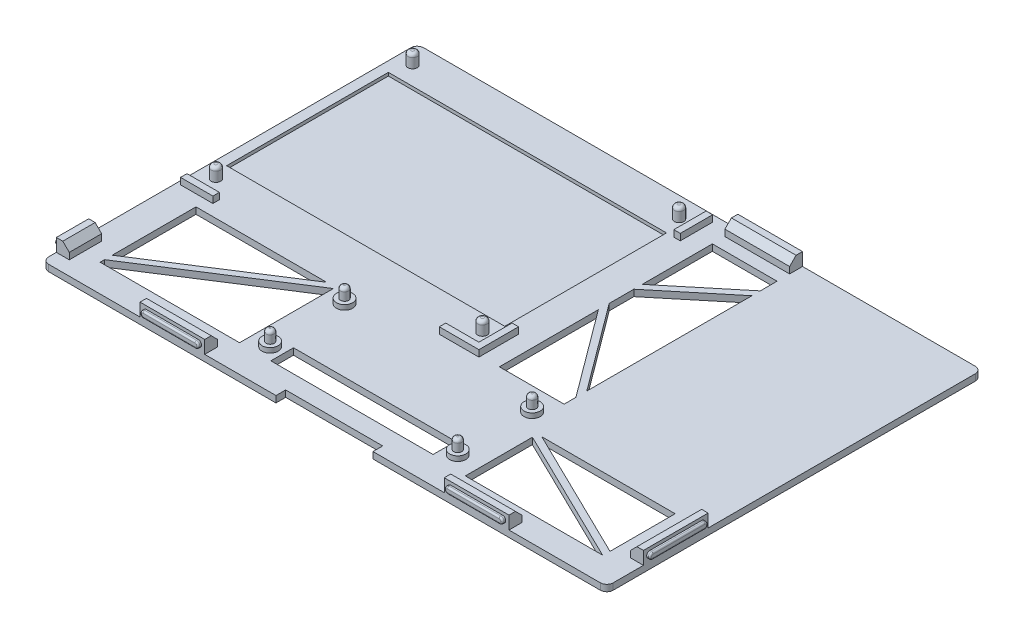
SolidWorks part; units mm, degrees
ref_plane "前基準面" through (0, 0, 0) normal (0, 0, 1) x (1, 0, 0)
ref_plane "上基準面" through (0, 0, 0) normal (0, 1, 0) x (1, 0, 0)
ref_plane "右基準面" through (0, 0, 0) normal (1, 0, 0) x (0, 0, -1)
sketch "草圖1" plane through (0, 0, 0) normal (0, 1, 0) x (1, 0, 0)
  line L0 (0, 57.975) -> (0, -57.975) construction
  line L1 (-87.275, 57.975) -> (87.275, 57.975)
  line L2 (-87.275, 57.975) -> (-87.275, -57.975)
  line L3 (-87.275, -57.975) -> (87.275, -57.975)
  line L4 (87.275, 57.975) -> (87.275, -57.975)
  line L5 (-87.275, 57.975) -> (87.275, -57.975) construction
  line L6 (-87.275, -57.975) -> (87.275, 57.975) construction
  line L7 (-87.275, 0) -> (87.275, 0) construction
  point P0 (0, 0)
  dimension "D1" = 174.55
  dimension "D2" = 115.95
extrude "填料-伸長1" add sketch "草圖1" along normal blind 2
sketch "草圖2" plane through (0, 2, 0) normal (0, 1, 0) x (1, 0, 0)
  line L1 (-86.16, 55.93) -> (3.84, 55.93)
  line L2 (-86.16, 55.93) -> (-86.16, -14.07)
  line L3 (-86.16, -14.07) -> (3.84, -14.07)
  line L4 (3.84, 55.93) -> (3.84, -14.07)
  line L5 (-86.16, 55.93) -> (3.84, -14.07) construction
  line L6 (-86.16, -14.07) -> (3.84, 55.93) construction
  line L8 (-41.16, 55.93) -> (-41.16, -14.07) construction
  line L9 (-86.16, 20.93) -> (3.84, 20.93) construction
  line L10 (0, 57.975) -> (0, -57.975) construction
  line L11 (-87.275, 0) -> (87.275, 0) construction
  point P0 (-41.16, 20.93)
  dimension "D1" = 90
  dimension "D2" = 70
  dimension "D3" = 41.16
  dimension "D4" = 20.93
sketch "草圖3" plane through (0, 2, 0) normal (0, 1, 0) x (1, 0, 0)
  line L0 (3.84, 55.93) -> (3.84, -14.07) construction
  line L1 (4.09, 55.93) -> (6.09, 55.93)
  line L2 (4.09, 55.93) -> (4.09, 45.93)
  line L3 (4.09, 45.93) -> (6.09, 45.93)
  line L4 (6.09, 55.93) -> (6.09, 45.93)
  line L5 (-86.16, -14.07) -> (3.84, -14.07) construction
  line L7 (4.09, -14.07) -> (4.09, -4.07)
  line L8 (4.09, -4.07) -> (6.09, -4.07)
  line L9 (6.09, -14.07) -> (6.09, -4.07)
  line L10 (6.09, -16.32) -> (-6.16, -16.32)
  line L11 (6.09, -16.32) -> (6.09, -15.07)
  line L12 (4.09, -14.32) -> (-6.16, -14.32)
  line L13 (-6.16, -16.32) -> (-6.16, -14.32)
  line L14 (3.84, -14.32) -> (3.84, -16.32) construction
  line L15 (4.09, -14.07) -> (4.09, -14.32)
  line L16 (6.09, -14.07) -> (6.09, -15.07)
  line L18 (-86.16, -16.32) -> (-76.16, -16.32)
  line L19 (-86.16, -16.32) -> (-86.16, -14.32)
  line L20 (-86.16, -14.32) -> (-76.16, -14.32)
  line L21 (-76.16, -16.32) -> (-76.16, -14.32)
  dimension "D1" = 2
  dimension "D2" = 10
  dimension "D3" = 0.25
  dimension "D4" = 2
  dimension "D5" = 2
  dimension "D6" = 2
  dimension "D8" = 0.25
  dimension "D9" = 10
  dimension "D11" = 10
extrude "填料-伸長2" add sketch "草圖3" along normal blind 2
sketch "草圖4" plane through (0, 2, 0) normal (0, 1, 0) x (1, 0, 0)
  line L1 (-86.16, 55.93) -> (3.84, 55.93) construction
  line L2 (3.84, 55.93) -> (3.84, -14.07) construction
  line L3 (-86.16, -14.07) -> (3.84, -14.07) construction
  line L4 (-41.16, 55.93) -> (-41.16, -14.07) construction
  circle A0 centre (0.04, 51.63) radius 1.45
  circle A1 centre (0.04, -9.17) radius 1.45
  circle A2 centre (-82.36, -9.17) radius 1.45
  circle A3 centre (-82.36, 51.63) radius 1.45
  dimension "D1" = 2.9
  dimension "D2" = 3.8
  dimension "D3" = 4.3
  dimension "D4" = 4.9
extrude "填料-伸長3" add sketch "草圖4" along normal blind 4
fillet "圓角2" radius 1 4 edges at (-82.36, 6, -53.08) (-82.36, 6, 7.72) (0.04, 6, 10.62) (0.04, 6, -50.18)
sketch "草圖6" plane through (0, 2, 0) normal (0, 1, 0) x (1, 0, 0)
  line L1 (35.1797, 56.0179) -> (85.1797, 56.0179)
  line L2 (35.1797, 56.0179) -> (35.1797, -24.9821)
  line L3 (35.1797, -24.9821) -> (85.1797, -24.9821)
  line L4 (85.1797, 56.0179) -> (85.1797, -24.9821)
  line L5 (35.1797, 56.0179) -> (85.1797, -24.9821) construction
  line L6 (35.1797, -24.9821) -> (85.1797, 56.0179) construction
  point P0 (60.1797, 15.5179)
  dimension "D1" = 81
  dimension "D2" = 50
sketch "草圖5" plane through (0, 2, 0) normal (0, 1, 0) x (1, 0, 0)
  line L0 (-86.16, 55.93) -> (3.84, -14.07) construction
  line L1 (-84.16, 45.93) -> (1.84, 45.93)
  line L2 (-84.16, 45.93) -> (-84.16, -4.07)
  line L3 (-84.16, -4.07) -> (1.84, -4.07)
  line L4 (1.84, 45.93) -> (1.84, -4.07)
  line L5 (-84.16, 45.93) -> (1.84, -4.07) construction
  line L6 (-84.16, -4.07) -> (1.84, 45.93) construction
  line L7 (-86.16, 55.93) -> (3.84, 55.93) construction
  line L8 (-86.16, 55.93) -> (-86.16, -14.07) construction
  point P0 (-41.16, 20.93)
  dimension "D1" = 10
  dimension "D2" = 2
extrude "除料-伸長1" cut sketch "草圖5" against normal blind 1
sketch "草圖7" plane through (0, 2, 0) normal (0, 1, 0) x (1, 0, 0)
  line L0 (0, 57.975) -> (0, -57.975) construction
  line L1 (-32.5, -19.275) -> (32.5, -19.275)
  line L2 (-32.5, -19.275) -> (-32.5, -49.475)
  line L3 (-32.5, -49.475) -> (32.5, -49.475)
  line L4 (32.5, -19.275) -> (32.5, -49.475)
  line L5 (-32.5, -19.275) -> (32.5, -49.475) construction
  line L6 (-32.5, -49.475) -> (32.5, -19.275) construction
  line L7 (-87.275, -57.975) -> (87.275, -57.975) construction
  point P0 (0, -34.375)
  point P5 (32.5, -34.375)
  dimension "D1" = 65
  dimension "D2" = 30.2
  dimension "D3" = 8.5
sketch "草圖8" plane through (0, 2, 0) normal (0, 1, 0) x (1, 0, 0)
  line L0 (-32.5, -19.275) -> (32.5, -19.275) construction
  line L1 (32.5, -19.275) -> (32.5, -49.475) construction
  line L2 (-32.5, -49.475) -> (32.5, -49.475) construction
  line L3 (0, -19.275) -> (0, -49.475) construction
  circle A0 centre (29, -22.775) radius 2.5
  circle A1 centre (29, -22.775) radius 1.25
  circle A2 centre (29, -45.775) radius 2.5
  circle A3 centre (29, -45.775) radius 1.25
  circle A4 centre (-29, -45.775) radius 1.25
  circle A5 centre (-29, -45.775) radius 2.5
  circle A6 centre (-29, -22.775) radius 1.25
  circle A7 centre (-29, -22.775) radius 2.5
  dimension "D1" = 5
  dimension "D4" = 2.5
  dimension "D2" = 3.5
  dimension "D3" = 3.5
  dimension "D5" = 3.7
extrude "填料-伸長4" add sketch "草圖8" along normal blind 1.5 contours A6 | A7 A6 | A5 A4 | A4 | A0 A1 | A1 | A2 A3 | A3 region at (26.5707, 2, 22.775) region at (29, 2, 22.775) region at (26.5707, 2, 45.775) region at (29, 2, 45.775) region at (-29, 2, 45.775) region at (-31.4293, 2, 45.775) region at (-29, 2, 22.775) region at (-31.4293, 2, 22.775)
extrude "填料-伸長5" add sketch "草圖8<3>" along normal blind 5 contours A6 | A4 | A3 | A1 region at (29, 2, 22.775) region at (29, 2, 45.775) region at (-29, 2, 45.775) region at (-29, 2, 22.775)
sketch "草圖8<3>" plane through (0, 2, 0) normal (0, 1, 0) x (1, 0, 0) same geometry as "草圖8"
fillet "圓角3" radius 1 4 edges at (-29, 7, 47.025) (29, 7, 47.025) (29, 7, 24.025) (-29, 7, 24.025)
sketch "草圖9" plane through (0, 2, 0) normal (0, 1, 0) x (1, 0, 0)
  line L0 (0, 57.975) -> (0, -57.975) construction
  line L1 (-25.0798, -42.475) -> (25.0798, -42.475)
  line L2 (-25.0798, -42.475) -> (-25.0798, -49.475)
  line L3 (-25.0798, -49.475) -> (25.0798, -49.475)
  line L4 (25.0798, -42.475) -> (25.0798, -49.475)
  line L5 (-25.0798, -42.475) -> (25.0798, -49.475) construction
  line L6 (-25.0798, -49.475) -> (25.0798, -42.475) construction
  line L7 (-32.5, -49.475) -> (32.5, -49.475) construction
  line L8 (-87.275, -57.975) -> (87.275, -57.975) construction
  line L9 (-15, -54.975) -> (15, -54.975)
  line L10 (-15, -54.975) -> (-15, -57.975)
  line L11 (-15, -57.975) -> (15, -57.975)
  line L12 (15, -54.975) -> (15, -57.975)
  line L13 (-15, -54.975) -> (15, -57.975) construction
  line L14 (-15, -57.975) -> (15, -54.975) construction
  point P0 (0, -45.975)
  point P9 (0, -56.475)
  dimension "D1" = 7
  dimension "D2" = 3
  dimension "D3" = 30
extrude "除料-伸長2" cut sketch "草圖9" against normal blind 2
sketch "草圖10" plane through (0, 2, 0) normal (0, 1, 0) x (1, 0, 0)
  line L0 (-87.275, 57.975) -> (87.275, 57.975) construction
  line L1 (11.8547, 57.975) -> (31.8547, 57.975)
  line L2 (11.8547, 57.975) -> (11.8547, 53.975)
  line L3 (11.8547, 53.975) -> (31.8547, 53.975)
  line L4 (31.8547, 57.975) -> (31.8547, 53.975)
  line L5 (0, 57.975) -> (0, -57.975) construction
  line L10 (87.275, 57.975) -> (87.275, -57.975) construction
  line L11 (87.275, -26.638) -> (83.275, -26.638)
  line L12 (87.275, -26.638) -> (87.275, -46.638)
  line L13 (87.275, -46.638) -> (83.275, -46.638)
  line L14 (83.275, -26.638) -> (83.275, -46.638)
  line L15 (-87.275, -57.975) -> (87.275, -57.975) construction
  line L16 (37.0319, -57.975) -> (57.0319, -57.975)
  line L17 (37.0319, -57.975) -> (37.0319, -53.975)
  line L18 (37.0319, -53.975) -> (57.0319, -53.975)
  line L19 (57.0319, -57.975) -> (57.0319, -53.975)
  line L20 (-57.0319, -57.975) -> (-57.0319, -53.975)
  line L21 (-37.0319, -53.975) -> (-57.0319, -53.975)
  line L22 (-37.0319, -57.975) -> (-37.0319, -53.975)
  line L23 (-37.0319, -57.975) -> (-57.0319, -57.975)
  line L24 (-87.275, 57.975) -> (-87.275, -57.975) construction
  line L25 (-87.275, -53.6) -> (-83.275, -53.6)
  line L26 (-87.275, -53.6) -> (-87.275, -43.6)
  line L27 (-87.275, -43.6) -> (-83.275, -43.6)
  line L28 (-83.275, -53.6) -> (-83.275, -43.6)
  dimension "D1" = 4
  dimension "D2" = 20
  dimension "D3" = 4
  dimension "D4" = 10
  dimension "D5" = 20
  dimension "D6" = 4
  dimension "D7" = 20
  dimension "D8" = 4
extrude "填料-伸長6" add sketch "草圖10" along normal blind 4
sketch "草圖11" plane through (0, 2, 0) normal (0, 1, 0) x (1, 0, 0)
  line L0 (-77.8796, -45.7226) -> (-37.4971, -19.8239)
  line L1 (-77.8796, -49.4672) -> (-34.7645, -49.4672)
  line L2 (-77.8796, -49.4672) -> (-77.8796, -48.0986)
  line L3 (-77.8796, -19.8239) -> (-37.4971, -19.8239)
  line L4 (-34.7645, -49.4672) -> (-34.7645, -20.4474)
  line L5 (-77.8796, -48.0986) -> (-34.7645, -20.4474)
  line L6 (-77.8796, -45.7226) -> (-77.8796, -19.8239)
  line L7 (31.8547, 44.9175) -> (11.8547, 28.4103)
  line L8 (11.8547, 50.0907) -> (31.8547, 50.0907)
  line L9 (11.8547, 50.0907) -> (11.8547, 28.4103)
  line L10 (11.8547, -15.7529) -> (31.8547, -15.7529)
  line L11 (31.8547, 50.0907) -> (31.8547, 44.9175)
  line L13 (11.8547, 25.8171) -> (31.8547, 42.3243)
  line L14 (11.8547, 18.1985) -> (31.8547, -8.7367)
  line L15 (11.8547, 14.8436) -> (31.8547, -12.0916)
  line L16 (31.8547, 42.3243) -> (31.8547, -8.7367)
  line L17 (11.8547, 25.8171) -> (11.8547, 18.1985)
  line L18 (11.8547, 14.8436) -> (11.8547, -15.7529)
  line L19 (31.8547, -12.0916) -> (31.8547, -15.7529)
  line L20 (78.3594, -48.0628) -> (37.1158, -27.9151)
  line L21 (37.1158, -27.9151) -> (78.3594, -27.9151)
  line L22 (35.8042, -29.5002) -> (35.8042, -50.2291)
  line L23 (35.8042, -50.2291) -> (78.2374, -50.2291)
  line L24 (78.3594, -27.9151) -> (78.3594, -48.0628)
  line L25 (35.8042, -29.5002) -> (78.2374, -50.2291)
  dimension "D1" = 2
  dimension "D2" = 2
  dimension "D3" = 2
  dimension "D4" = 2
extrude "除料-伸長3" cut sketch "草圖11" against normal through all
fillet "圓角1" radius 2 4 edges at (87.275, 1, -57.975) (-87.275, 1, -57.975) (-87.275, 1, 57.975) (87.275, 1, 57.975)
chamfer "導角1" distance 2 angle 45 5 edges at (83.275, 6, 36.638) (47.0319, 6, 53.975) (-47.0319, 6, 53.975) (-83.275, 6, 48.6) (21.8547, 6, -53.975)
sketch "草圖13" plane through (87.275, 0, 0) normal (1, 0, 0) x (0, 0, -1)
  line L0 (-44.638, 4) -> (-28.638, 4) construction
  line L1 (-44.638, 5) -> (-28.638, 5)
  line L2 (-44.638, 3) -> (-28.638, 3)
  line L4 (-46.638, 4) -> (-26.638, 4) construction
  line L5 (-46.638, 6) -> (-46.638, 2) construction
  arc A0 (-44.638, 5) -> (-44.638, 3) centre (-44.638, 4) ccw
  arc A1 (-28.638, 3) -> (-28.638, 5) centre (-28.638, 4) ccw
  point P2 (-36.638, 4)
  point P16 (-36.638, 4)
  dimension "D1" = 2
  dimension "D2" = 16
extrude "填料-伸長8" add sketch "草圖13" along normal blind 1
sketch "草圖14" plane through (0, 0, -57.975) normal (0, 0, -1) x (-1, 0, 0)
  line L0 (-31.8547, 4) -> (-11.8547, 4) construction
  line L1 (-31.8547, 6) -> (-31.8547, 2) construction
  line L2 (-29.8547, 4) -> (-13.8547, 4) construction
  line L3 (-29.8547, 5) -> (-13.8547, 5)
  line L4 (-29.8547, 3) -> (-13.8547, 3)
  arc A0 (-29.8547, 5) -> (-29.8547, 3) centre (-29.8547, 4) ccw
  arc A1 (-13.8547, 3) -> (-13.8547, 5) centre (-13.8547, 4) ccw
  point P7 (-21.8547, 4)
  point P13 (-21.8547, 4)
  dimension "D1" = 16
  dimension "D2" = 2
extrude "填料-伸長9" add sketch "草圖14" along normal blind 1
sketch "草圖15" plane through (0, 0, 57.975) normal (0, 0, 1) x (1, 0, 0)
  line L0 (-57.0319, 4) -> (-37.0319, 4) construction
  line L1 (-57.0319, 6) -> (-57.0319, 2) construction
  line L2 (-37.0319, 6) -> (-37.0319, 2) construction
  line L3 (-55.0319, 4) -> (-39.0319, 4) construction
  line L4 (-55.0319, 5) -> (-39.0319, 5)
  line L5 (-55.0319, 3) -> (-39.0319, 3)
  line L6 (0, 2) -> (0, 0) construction
  line L7 (55.0319, 4) -> (39.0319, 4) construction
  line L8 (55.0319, 5) -> (39.0319, 5)
  line L9 (55.0319, 3) -> (39.0319, 3)
  arc A0 (-55.0319, 5) -> (-55.0319, 3) centre (-55.0319, 4) ccw
  arc A1 (-39.0319, 3) -> (-39.0319, 5) centre (-39.0319, 4) ccw
  arc A2 (55.0319, 5) -> (55.0319, 3) centre (55.0319, 4) cw
  arc A3 (39.0319, 3) -> (39.0319, 5) centre (39.0319, 4) cw
  point P8 (-47.0319, 4)
  point P16 (47.0319, 4)
  dimension "D1" = 16
  dimension "D2" = 2
extrude "填料-伸長11" add sketch "草圖15" along normal blind 1
sketch "草圖16" plane through (-87.275, 0, 0) normal (-1, 0, 0) x (0, 0, 1)
  line L0 (43.6, 4) -> (53.6, 4) construction
  line L1 (43.6, 6) -> (43.6, 2) construction
  line L2 (53.6, 6) -> (53.6, 2) construction
  line L3 (45.1, 4) -> (52.1, 4) construction
  line L4 (45.1, 5) -> (52.1, 5)
  line L5 (45.1, 3) -> (52.1, 3)
  arc A0 (45.1, 5) -> (45.1, 3) centre (45.1, 4) ccw
  arc A1 (52.1, 3) -> (52.1, 5) centre (52.1, 4) ccw
  point P8 (48.6, 4)
  dimension "D1" = 7
  dimension "D2" = 2
extrude "填料-伸長12" add sketch "草圖16" along normal blind 1
fillet "圓角4" radius 0.5 20 edges at (12.8547, 4, -58.975) (21.8547, 3, -58.975) (30.8547, 4, -58.975) (88.275, 4, 27.638) (88.275, 3, 36.638) (88.275, 4, 45.638) (56.0319, 4, 58.975) (47.0319, 3, 58.975) (38.0319, 4, 58.975) (-88.275, 4, 53.1) (-88.275, 3, 48.6) (-88.275, 4, 44.1) (-38.0319, 4, 58.975) (-47.0319, 3, 58.975) (-56.0319, 4, 58.975) (21.8547, 5, -58.975) (88.275, 5, 36.638) (47.0319, 5, 58.975) (-88.275, 5, 48.6) (-47.0319, 5, 58.975)
